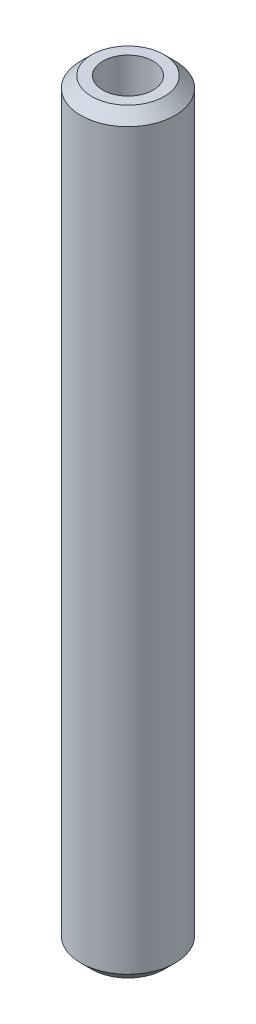
SolidWorks part; units mm, degrees
ref_plane "Front Plane" through (0, 0, 0) normal (0, 0, 1) x (1, 0, 0)
ref_plane "Top Plane" through (0, 0, 0) normal (0, 1, 0) x (1, 0, 0)
ref_plane "Right Plane" through (0, 0, 0) normal (1, 0, 0) x (0, 0, -1)
sketch "Sketch1" plane through (0, 0, 0) normal (0, 1, 0) x (1, 0, 0)
  circle A0 centre (0, 0) radius 5
  dimension "SHAFT_OD" = 10
extrude "Boss-Extrude1" add sketch "Sketch1" along normal blind 80.1344
sketch "Sketch2" plane through (0, 0, 0) normal (0, 1, 0) x (1, 0, 0)
  circle A0 centre (0, 0) radius 2.665
  dimension "BORE_D" = 5.3299
extrude "Cut-Extrude1" cut sketch "Sketch2" along normal through all
chamfer "Chamfer1" distance 1.1587 angle 45 2 edges at (0, 80.1344, 5) (0, 0, 5)
